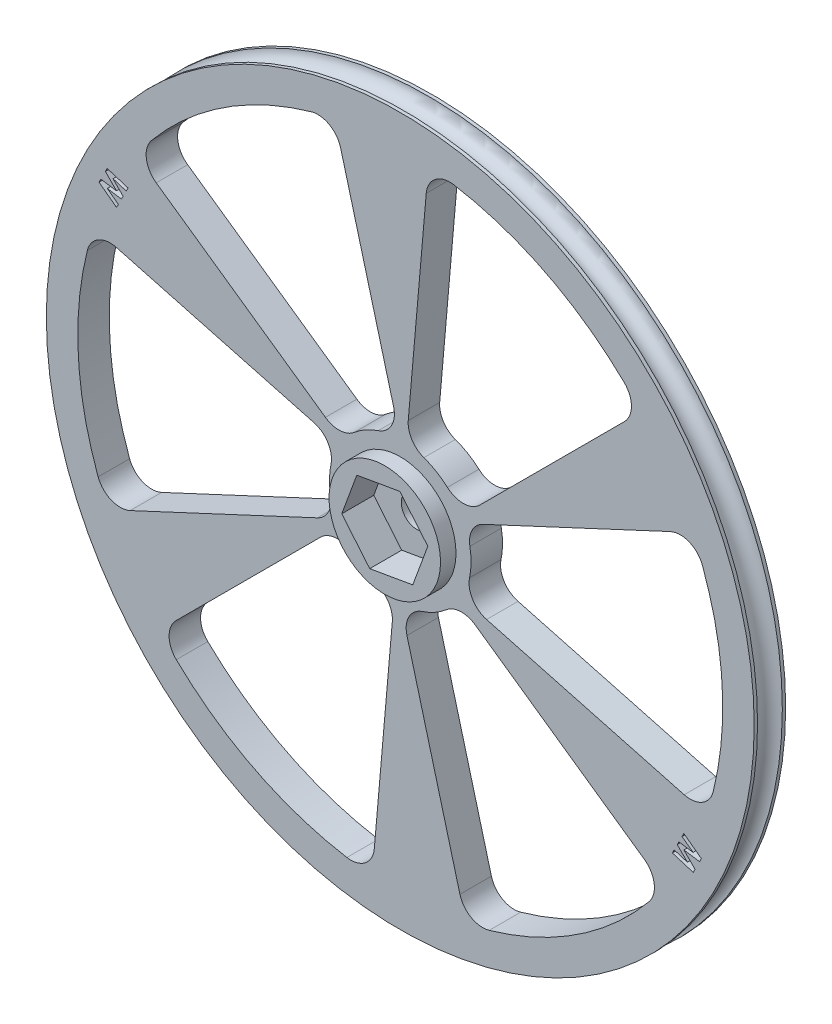
SolidWorks part; units mm, degrees
ref_plane "Front Plane" through (0, 0, 0) normal (0, 0, 1) x (1, 0, 0)
ref_plane "Top Plane" through (0, 0, 0) normal (0, 1, 0) x (1, 0, 0)
ref_plane "Right Plane" through (0, 0, 0) normal (1, 0, 0) x (0, 0, -1)
sketch "Sketch1" plane through (0, 0, 0) normal (0, 0, 1) x (1, 0, 0)
  circle A0 centre (0, 0) radius 57.15
  dimension "D1" = 114.3
extrude "Boss-Extrude3" add sketch "Sketch1" along normal mid plane 5.08
sketch "Sketch3" plane through (0, 0, 2.54) normal (0, 0, 1) x (1, 0, 0)
  line L0 (0, -1000) -> (0, 49000) construction
  line L1 (-1000, 0) -> (49000, 0) construction
  line L2 (-42.6532, 29.8661) -> (-9.3629, 6.556)
  line L3 (-10.5974, 50.9802) -> (0, 11.43)
  line L4 (-9.3629, 6.556) -> (0, 0) construction
  line L5 (0, 0) -> (0, 11.43)
  arc A0 (-42.6532, 29.8661) -> (-10.5974, 50.9802) centre (0, 0) cw
  arc A1 (0, 11.43) -> (-9.3629, 6.556) centre (0, 0) ccw
  circle A2 centre (0, 0) radius 57.15 construction
  dimension "D1" = 52.07
  dimension "D2" = 11.43
  dimension "D3" = 15
  dimension "D4" = 55
extrude "Cut-Extrude1" cut sketch "Sketch3" against normal through all both and the other way through all contours A1 L3 A0 L2 region at (-18.6851, 29.2, 2.54)
fillet "Fillet1" radius 3.81 4 edges at (-9.3629, 6.556, 0) (-42.6532, 29.8661, 0) (0, 11.43, 0) (-10.5974, 50.9802, 0)
pattern_circular "CirPattern1" count 6 over 360 about axis through (0, 0, 2.54) along (0, 0, -1) of "Cut-Extrude1", "Fillet1"
sketch "Sketch4" plane through (0, 0, 2.54) normal (0, 0, 1) x (1, 0, 0)
  circle A0 centre (0, 0) radius 2.5
  dimension "D1" = 5
extrude "Cut-Extrude2" cut sketch "Sketch4" against normal through all both and the other way through all contours A0
sketch "Sketch5" plane through (0, 0, 2.54) normal (0, 0, 1) x (1, 0, 0)
  line L1 (4.5151, -5.4145) -> (6.9466, 1.2029)
  line L2 (6.9466, 1.2029) -> (2.4316, 6.6174)
  line L3 (2.4316, 6.6174) -> (-4.5151, 5.4145)
  line L4 (-4.5151, 5.4145) -> (-6.9466, -1.2029)
  line L5 (-6.9466, -1.2029) -> (-2.4316, -6.6174)
  line L6 (-2.4316, -6.6174) -> (4.5151, -5.4145)
  circle A0 centre (0, 0) radius 9
  circle A1 centre (0, 0) radius 6.1055 construction
  dimension "D1" = 18
  dimension "D2" = 7.05
extrude "Cut-Extrude3" cut sketch "Sketch5" against normal mid plane 5.334 contours L2 L3 L4 L5 L6 L1
extrude "Boss-Extrude9" add sketch "Sketch5<3>" along normal blind 2.5
sketch "Sketch5<3>" plane through (0, 0, 2.54) normal (0, 0, 1) x (1, 0, 0) same geometry as "Sketch5"
sketch "Sketch11" plane through (0, 0, 0) normal (1, 0, 0) x (0, 0, -1)
  circle A0 centre (0, 57.15) radius 2
  dimension "D1" = 4
  dimension "D2" = 57.15
revolve "Cut-Revolve1" cut sketch "Sketch11" angle 360 about axis through (0, 0, 5.04) along (0, 0, -1)
sketch "Sketch12" plane through (0, 0, 2.54) normal (0, 0, 1) x (1, 0, 0)
  line L0 (-41.0336, 30.7154) -> (-48.7628, 14.9486) construction
  line L1 (48.7628, -14.9486) -> (40.9989, -30.2025) construction
  arc A2 (-45.8427, 15.3462) -> (-50.5258, 12.587) centre (-46.8288, 11.666) ccw construction
  arc A3 (-40.1623, 33.1403) -> (-39.4089, 27.5944) centre (-37.2236, 30.7154) ccw construction
  arc A4 (45.8427, -15.3462) -> (50.5258, -12.587) centre (46.8288, -11.666) ccw construction
  arc A5 (40.1623, -33.1403) -> (39.4089, -27.5944) centre (37.2236, -30.7154) ccw construction
  text T0 "<b>M</b>"
  text T1 "<b>M</b>"
extrude "Cut-Extrude4" cut sketch "Sketch12" against normal through all
